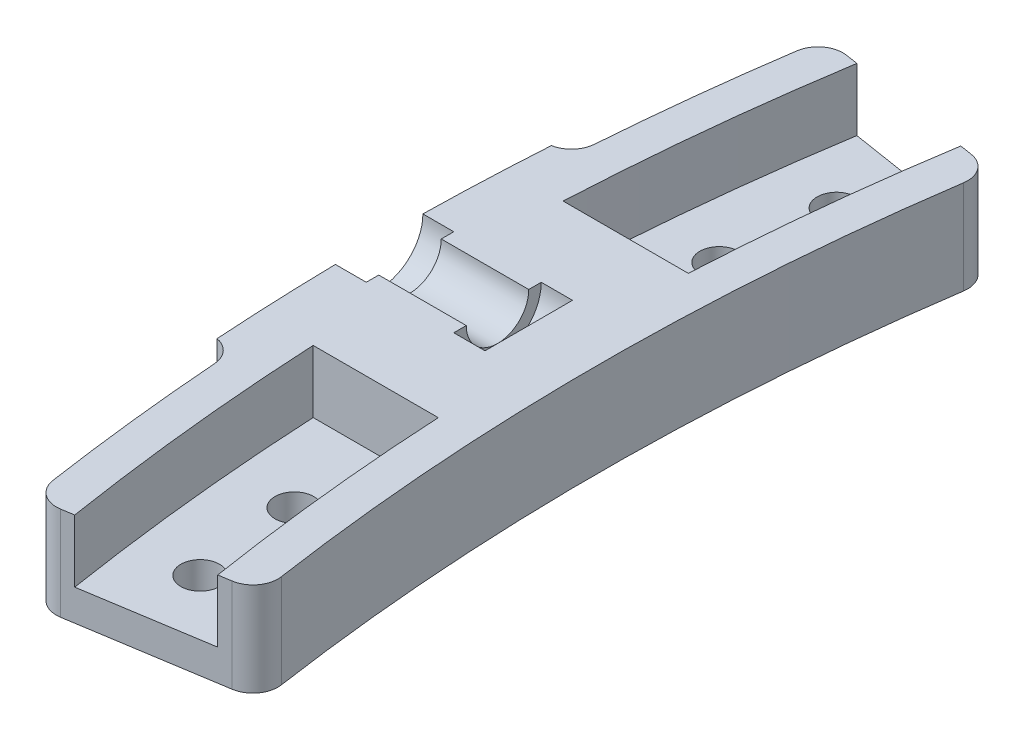
SolidWorks part; units mm, degrees
ref_plane "Front Plane" through (0, 0, 0) normal (0, 0, 1) x (1, 0, 0)
ref_plane "Top Plane" through (0, 0, 0) normal (0, 1, 0) x (1, 0, 0)
ref_plane "Right Plane" through (0, 0, 0) normal (1, 0, 0) x (0, 0, -1)
sketch "Sketch1" plane through (0, 0, 0) normal (0, 1, 0) x (1, 0, 0)
  line L0 (0, 0) -> (-197.5377, -31.2869) construction
  line L1 (0, 0) -> (-197.5377, 31.2869) construction
  line L2 (0, 0) -> (-195, 0) construction
  line L3 (-197.5377, 31.2869) -> (-187.6608, 29.7225)
  line L4 (-187.6608, -29.7225) -> (-197.5377, -31.2869)
  line L5 (0, 0) -> (-200.5007, -31.7562) construction
  line L6 (0, 0) -> (-200.5007, 31.7562) construction
  line L7 (-200.5007, 31.7562) -> (-184.6977, 29.2532)
  line L8 (-200.5007, -31.7562) -> (-184.6977, -29.2532)
  arc A0 (-197.5377, 31.2869) -> (-197.5377, -31.2869) centre (0, 0) ccw
  arc A1 (-187.6608, 29.7225) -> (-187.6608, -29.7225) centre (0, 0) ccw
  arc A2 (-192.5992, -30.5047) -> (-192.5992, 30.5047) centre (0, 0) cw construction
  arc A4 (-184.6977, 29.2532) -> (-184.6977, -29.2532) centre (0, 0) ccw
  arc A5 (-200.5007, 31.7562) -> (-200.5007, -31.7562) centre (0, 0) ccw
  dimension "D1" = 200
  dimension "D2" = 190
  dimension "D3" = 5
  dimension "D5" = 187
  dimension "D6" = 203
  dimension "D4" = 18
extrude "Boss-Extrude1" add sketch "Sketch1" along normal blind 7.5 contours A1 L3 A0 L4 | L7 A5 L8 A0 | A4 L7 A1 L8 region at (-200.6761, 0, 0) region at (-194.2416, 0, 0) region at (-187.7297, 0, 0)
ref_plane "Plane1" through (-195, 0, 0) normal (1, 0, 0) x (0, 0, -1)
sketch "Sketch19" plane through (0, 0, 0) normal (0, 1, 0) x (1, 0, 0)
  line L0 (0, 0) -> (-204.0621, 13.3749) construction
  line L1 (0, 0) -> (-204.0621, -13.3749) construction
  line L4 (0, 0) -> (-204.5, 0) construction
  line L5 (-204.0621, 13.3749) -> (-202.5654, 13.2768)
  line L6 (-204.0621, -13.3749) -> (-202.5654, -13.2768)
  arc A0 (-204.0621, 13.3749) -> (-204.0621, -13.3749) centre (0, 0) ccw
  arc A1 (-200.5007, 31.7562) -> (-200.5007, -31.7562) centre (0, 0) ccw construction
  arc A2 (-202.5654, 13.2768) -> (-202.5654, -13.2768) centre (0, 0) ccw
  dimension "D1" = 204.5
  dimension "D2" = 3.75
extrude "Boss-Extrude2" add sketch "Sketch19" along normal blind 7.5
sketch "Sketch15" plane through (0, 7.5, 0) normal (0, 1, 0) x (1, 0, 0)
  line L0 (-187.6608, -29.7225) -> (-197.5377, -31.2869) construction
  line L1 (-185, 10) -> (-205, 10)
  line L2 (-185, 10) -> (-185, -10)
  line L3 (-185, -10) -> (-205, -10)
  line L4 (-205, 10) -> (-205, -10)
  line L5 (-185, 10) -> (-205, -10) construction
  line L6 (-185, -10) -> (-205, 10) construction
  line L7 (-197.5377, 31.2869) -> (-187.6608, 29.7225) construction
  line L8 (-187.6608, -29.7225) -> (-197.5377, -31.2869)
  line L9 (-197.5377, 31.2869) -> (-187.6608, 29.7225)
  arc A2 (-187.6608, 29.7225) -> (-187.6608, -29.7225) centre (0, 0) ccw construction
  arc A3 (-197.5377, 31.2869) -> (-197.5377, -31.2869) centre (0, 0) ccw construction
  arc A4 (-187.6608, 29.7225) -> (-187.6608, -29.7225) centre (0, 0) ccw
  arc A5 (-197.5377, 31.2869) -> (-197.5377, -31.2869) centre (0, 0) ccw
  point P0 (-195, 0)
  line M5 (-200.5007, -31.7562) -> (-184.6977, -29.2532)
  line M7 (-184.6977, 29.2532) -> (-200.5007, 31.7562)
  dimension "D1" = 20
  dimension "D2" = 20
extrude "Cut-Extrude1" cut sketch "Sketch15" against normal blind 5 contours A5 L1 A4 M7 | L3 A5 A4 M5 region at (-193.9153, 7.5, -20.2762) region at (-193.9153, 7.5, 20.2762)
ref_plane "Plane2" through (-195, 0, 0) normal (-1, 0, 0) x (0, 0, 1)
sketch "Sketch12" plane through (0, 0, 0) normal (0, 1, 0) x (1, 0, 0)
  line L0 (0, 0) -> (-194.258, -16.9954) construction
  line L1 (0, 0) -> (-193.3317, -25.4526) construction
  line L2 (0, 0) -> (-195, 0) construction
  line L3 (0, 0) -> (-195, 0) construction
  line L4 (0, 0) -> (-194.258, 16.9954) construction
  line L5 (0, 0) -> (-193.3317, 25.4526) construction
  arc A0 (-192.5992, 30.5047) -> (-192.5992, -30.5047) centre (0, 0) ccw construction
  dimension "D1" = 10
  dimension "D2" = 15
hole_wizard "Ø3.1 (3.1) Diameter Hole2" positions "Sketch18" profile "Sketch17" hole size "Ø3.1" standard "ISO" end condition through all
sketch "Sketch18" plane through (0, 0, 0) normal (0, -1, 0) x (-1, 0, 0)
  point P0 (193.3317, -25.4526)
  point P3 (194.258, -16.9954)
  point P6 (194.258, 16.9954)
  point P9 (193.3317, 25.4526)
sketch "Sketch17" plane through (-193.3317, 0, 25.4526) normal (1, 0, 0) x (0, 0, -1)
  line L0 (0, 0) -> (0, 7.5)
  line L1 (0, 7.5) -> (1.55, 7.5)
  line L2 (1.55, 7.5) -> (1.55, 0)
  line L5 (1.55, 0) -> (0, 0)
  line L11 (0, -6.35) -> (0, 107.95) construction
  dimension "Thru Hole Dia." = 3.1
  dimension "Thru Hole Depth" = 7.5
sketch "Sketch20" plane through (0, 0, 0) normal (0, 1, 0) x (1, 0, 0)
  line L0 (-205, 0) -> (-192.5, 0) construction
  line L1 (0, 0) -> (-205, 0) construction
  arc A2 (-204.0621, 13.3749) -> (-204.0621, -13.3749) centre (0, 0) ccw construction
  point P3 (-204.5, 0)
  dimension "D1" = 205
  dimension "D2" = 12.5
ref_plane "Plane3" through (-192.5, 0, 0) normal (1, 0, 0) x (0, 0, -1)
sketch "Sketch21" plane through (-192.5, 0, 0) normal (1, 0, 0) x (0, 0, -1)
  line L0 (29.2532, 7.5) -> (-29.2532, 7.5) construction
  circle A0 centre (0, 7.5) radius 3.5
  dimension "D1" = 7
extrude "Cut-Extrude2" cut sketch "Sketch21" against normal blind 2.5
sketch "Sketch22" plane through (-195, 0, 0) normal (1, 0, 0) x (0, 0, -1)
  line L0 (29.2532, 7.5) -> (-29.2532, 7.5) construction
  circle A0 centre (0, 7.5) radius 2.5
  dimension "D1" = 5
ref_plane "Plane4" through (-204.5, 0, 0) normal (1, 0, 0) x (0, 0, -1)
sketch "Sketch23" plane through (-204.5, 0, 0) normal (1, 0, 0) x (0, 0, -1)
  circle A0 centre (0, 7.5) radius 3.5
  dimension "D1" = 7
extrude "Cut-Extrude3" cut sketch "Sketch23" along normal blind 2.5
extrude "Cut-Extrude4" cut sketch "Sketch22" against normal through all contours A0
fillet "Fillet1" radius 2 4 edges at (-200.5007, 3.75, -31.7562) (-184.6977, 3.75, -29.2532) (-184.6977, 3.75, 29.2532) (-200.5007, 3.75, 31.7562)
fillet "Fillet2" radius 2 2 edges at (-202.5654, 3.75, -13.2768) (-202.5654, 3.75, 13.2768)
